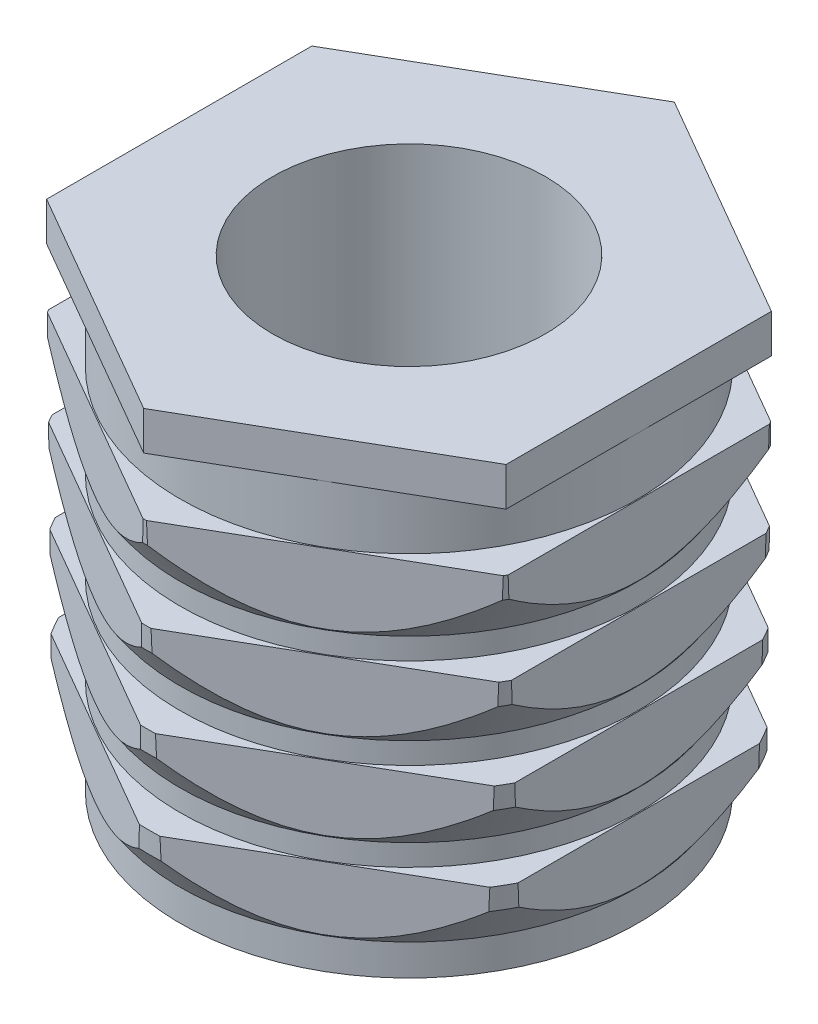
SolidWorks part; units mm, degrees
ref_plane "Front Plane" through (0, 0, 0) normal (0, 0, 1) x (1, 0, 0)
ref_plane "Top Plane" through (0, 0, 0) normal (0, 1, 0) x (1, 0, 0)
ref_plane "Right Plane" through (0, 0, 0) normal (1, 0, 0) x (0, 0, -1)
sketch "Sketch1" plane through (0, 0, 0) normal (0, 1, 0) x (1, 0, 0)
  line L0 (-3.945, 0) -> (3.945, 0) construction
  line L1 (-3.945, 0) -> (-3.96, 0) construction
  line L2 (0, 4.5726) -> (-3.96, 2.2863)
  line L3 (-3.96, 2.2863) -> (-3.96, -2.2863)
  line L4 (-3.96, -2.2863) -> (0, -4.5726)
  line L5 (0, -4.5726) -> (3.96, -2.2863)
  line L6 (3.96, -2.2863) -> (3.96, 2.2863)
  line L7 (3.96, 2.2863) -> (0, 4.5726)
  line L8 (3.945, 0) -> (3.96, 0) construction
  line L9 (-4.5726, 0) -> (-3.96, 0) construction
  circle A0 centre (0, 0) radius 3.945 construction
  circle A1 centre (0, 0) radius 3.96 construction
  circle A2 centre (0, 0) radius 4.5726 construction
  dimension "OD" = 7.89
  dimension "Hex" = 7.92
extrude "Extrude1" add sketch "Sketch1" against normal blind 8
sketch "Sketch2" plane through (0, 0, 0) normal (0, 1, 0) x (1, 0, 0)
  circle A2 centre (0, 0) radius 3
  point P0 (-3, 0)
  dimension "Internal Thread OD" = 6
curve "Helix/Spiral1" [suppressed] pitch 1 height 9.5381 turns 9.5381 parameters "Internal Thread Height"=9.5381, "Internal Thread Pitch"=1
sketch "Sketch3" plane through (0, 0, 0) normal (0, 0, 1) x (1, 0, 0)
  line L0 (-2.2422, 0.5625) -> (-2.2422, -0.4375) construction
  line L1 (-2.2422, -0.4375) -> (-3.1083, 0.0625) construction
  line L2 (-3.1083, 0.0625) -> (-2.2422, 0.5625) construction
  line L3 (-2.2422, 0.0625) -> (-2.3505, 0.0625) construction
  line L4 (-2.3505, 0.0625) -> (-3, 0.0625) construction
  line L5 (-3, 0.0625) -> (-3.1083, 0.0625) construction
  line L6 (-3, 0.125) -> (-3, 0)
  line L7 (-2.3505, -0.375) -> (-2.3505, 0.5) construction
  line L11 (-3, 0) -> (-2.2964, -0.4062)
  line L12 (-2.2964, -0.4062) -> (-2.2964, 0.5312)
  line L13 (-2.2964, 0.5312) -> (-3, 0.125)
  point P18 (-2.2964, 0.0625)
  dimension "D1" = 1
  dimension "D2" = 0.125
sketch "Sketch4" plane through (0, 0, 0) normal (0, 1, 0) x (-1, 0, 0)
  circle A0 centre (0, 0) radius 2.3505
extrude "Extrude2" cut sketch "Sketch4" against normal through all
chamfer "Chamfer1" [suppressed] distance 0.75 angle 45
sketch "Sketch5" plane through (0, 0, 0) normal (0, 0, 1) x (1, 0, 0)
  line L0 (4.5726, 0) -> (-4.5726, 0) construction
  line L1 (-3.945, 0) -> (-3.945, -8) construction
  line L2 (-3.945, 0) -> (-4.5726, 0) construction
  line L3 (0, 0) -> (0, -8) construction
  line L4 (-3.96, -8) -> (0, -8) construction
  line L5 (-3.945, -8) -> (-4.5726, -8)
  line L6 (-4.5726, 0) -> (-3.96, 0) construction
  line L7 (-4.5726, 0) -> (-4.5726, -8) construction
  line L8 (-4.5726, -0.6667) -> (-4.4446, -8) construction
  line L9 (-4.5726, -0.6667) -> (-3.945, -0.6667)
  line L10 (-4.5726, 0) -> (-4.5726, -0.6667)
  line L11 (-3.945, -0.6667) -> (-3.945, -1.6667)
  line L12 (-4.4936, -5.1957) -> (-3.945, -5.9791)
  line L13 (-3.945, -8) -> (-3.945, -7.4624)
  line L14 (-3.945, -5.9791) -> (-3.945, -6.348)
  line L15 (-3.945, -1.6667) -> (-4.5552, -1.6667)
  line L16 (-4.5552, -1.6667) -> (-4.5487, -2.0355)
  line L17 (-4.5487, -2.0355) -> (-3.945, -2.8977)
  line L18 (-3.945, -6.348) -> (-4.4734, -6.348)
  line L19 (-4.5726, 0) -> (-5.2002, 0)
  line L20 (-5.2002, 0) -> (-5.2002, -8)
  line L21 (-5.2002, -8) -> (-4.5726, -8)
  line L22 (-3.945, -3.2667) -> (-4.5272, -3.2667)
  line L23 (-3.945, -2.8977) -> (-3.945, -3.2667)
  line L24 (-4.5272, -3.2667) -> (-4.5208, -3.6355)
  line L25 (-4.5208, -3.6355) -> (-3.945, -4.4579)
  line L26 (-3.945, -4.8268) -> (-4.5, -4.8268)
  line L27 (-4.5, -4.8268) -> (-4.4936, -5.1957)
  line L28 (-4.4734, -6.348) -> (-4.467, -6.7169)
  line L29 (-3.945, -4.4579) -> (-3.945, -4.8268)
  line L30 (-4.467, -6.7169) -> (-3.945, -7.4624)
  dimension "D1" = 0.6667
  dimension "D2" = 1
  dimension "D5" = 35
  dimension "D6" = 1
  dimension "D3" = 1.6
revolve "Cut-Revolve1" cut sketch "Sketch5" angle 360 about L3
sketch "Sketch6" [suppressed] plane through (0, 0, 0) normal (0, 1, 0) x (1, 0, 0)
  line L0 (0, 0) -> (2.1924, -2.1924) construction
  line L1 (0, 0) -> (0, -4.5726) construction
  circle A0 centre (0, 0) radius 3.1005 construction
  point P8 (2.1924, -2.1924)
  dimension "D1" = 45
ref_plane "Contact Plane 1" through (0, 0, 0) normal (0, 1, 0) x (1, 0, 0)
ref_plane "Contact Plane 2" through (0, -8, 0) normal (0, -1, 0) x (-1, 0, 0)
ref_axis "Center Axis 1" [suppressed] through (0, -7.25, 0) along (0, 1, 0)
sweep "Cut-Sweep1" [suppressed] cut profiles "Sketch3" path "Helix/Spiral1"
equation "\"Internal Thread Height@Helix/Spiral1\" = \"Internal Thread Pitch@Helix/Spiral1\" + \"Length@Extrude1\" + 0.5381"
equation "\"D1@Sketch3\" = \"Internal Thread Pitch@Helix/Spiral1\""
equation "\"D2@Sketch3\" = \"D1@Sketch3\" * 1 / 8"
equation "\"D1@Chamfer1\" = \"Internal Thread Pitch@Helix/Spiral1\" * 6 / 8"
equation "\"D1@Sketch5\" = \"Length@Extrude1\"  * 1 / 12"
equation "\"D6@Sketch5\" = \"D1@Sketch5\" * 1.5"
equation "\"D3@Sketch5\" = \"Length@Extrude1\"  * 1 / 5"
